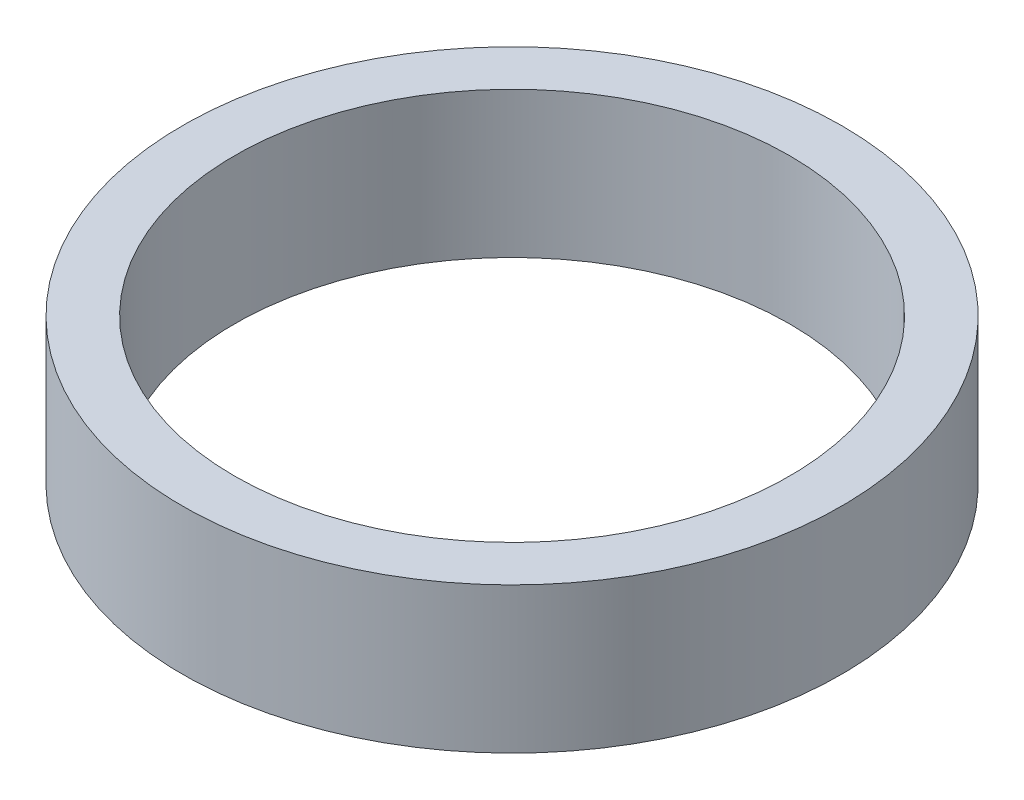
SolidWorks part; units mm, degrees
ref_plane "Front Plane" through (0, 0, 0) normal (0, 0, 1) x (1, 0, 0)
ref_plane "Top Plane" through (0, 0, 0) normal (0, 1, 0) x (1, 0, 0)
ref_plane "Right Plane" through (0, 0, 0) normal (1, 0, 0) x (0, 0, -1)
sketch "Sketch1" plane through (0, 0, 0) normal (0, 1, 0) x (1, 0, 0)
  circle A0 centre (0, 0) radius 47.5
  dimension "FLANGE_OD" = 95
extrude "Boss-Extrude1" add sketch "Sketch1" along normal blind 21
sketch "Sketch2" plane through (0, 0, 0) normal (0, 1, 0) x (1, 0, 0)
  circle A0 centre (0, 0) radius 40
  dimension "BORE_D" = 80
extrude "Cut-Extrude1" cut sketch "Sketch2" along normal through all
sketch "Sketch3" plane through (0, 21, 0) normal (0, 1, 0) x (1, 0, 0)
  circle A0 centre (0, 0) radius 21.72 construction
  circle A1 centre (-21.72, 0) radius 1.5
  dimension "BOLT_D" = 3
  dimension "BOLT_PCD" = 43.4399
extrude "Cut-Extrude2" cut sketch "Sketch3" against normal blind 19.5687 rebuild error yes
pattern_circular "CirPattern1" count 5 over 360 rebuild error yes
